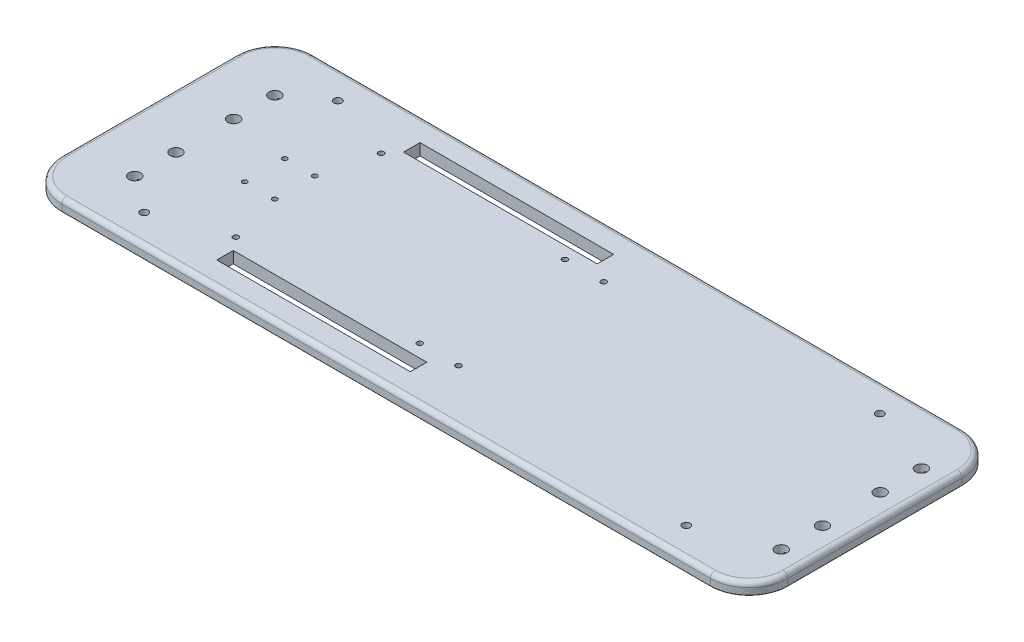
SolidWorks part; units mm, degrees
ref_plane "Alzado" through (0, 0, 0) normal (0, 0, 1) x (1, 0, 0)
ref_plane "Planta" through (0, 0, 0) normal (0, 1, 0) x (1, 0, 0)
ref_plane "Vista lateral" through (0, 0, 0) normal (1, 0, 0) x (0, 0, -1)
sketch "Croquis1" plane through (0, 0, 0) normal (0, 1, 0) x (1, 0, 0)
  line L1 (-187.5, -65) -> (187.5, -65)
  line L2 (-187.5, -65) -> (-187.5, 65)
  line L3 (-187.5, 65) -> (187.5, 65)
  line L4 (187.5, -65) -> (187.5, 65)
  line L5 (-187.5, -65) -> (187.5, 65) construction
  line L6 (-187.5, 65) -> (187.5, -65) construction
  point P0 (0, 0)
  dimension "D1" = 375
  dimension "D2" = 130
extrude "Saliente-Extruir1" add sketch "Croquis1" along normal blind 6
sketch "Croquis2" plane through (0, 6, 0) normal (0, 1, 0) x (1, 0, 0)
  line L0 (-158.7, -36.2) -> (-158.7, -14.9) construction
  line L1 (-187.5, -65) -> (-158.7, -65) construction
  line L2 (-187.5, -65) -> (-187.5, -36.2) construction
  line L3 (-187.5, -36.2) -> (-158.7, -36.2) construction
  line L4 (-158.7, -65) -> (-158.7, -36.2) construction
  line L5 (-55, 0) -> (55, 0) construction
  circle A0 centre (-158.7, -36.2) radius 3
  circle A1 centre (-158.7, -14.9) radius 1.5
  circle A2 centre (-158.7, 36.2) radius 3
  circle A3 centre (-158.7, 14.9) radius 1.5
  dimension "D3" = 6
  dimension "D5" = 3
  dimension "D1" = 28.8
  dimension "D2" = 28.8
  dimension "D4" = 21.3
extrude "Cortar-Extruir1" cut sketch "Croquis2" against normal blind 10
sketch "Croquis3" plane through (0, 6, 0) normal (0, 1, 0) x (1, 0, 0)
  line L0 (-158.7, -36.2) -> (187.5, -36.2) construction
  line L1 (187.5, -65) -> (187.5, 65) construction
  line L2 (175.3, -36.2) -> (175.3, -14.9) construction
  line L3 (175.3, -14.9) -> (-158.7, -14.9) construction
  line L4 (-55, 0) -> (55, 0) construction
  circle A0 centre (175.3, -36.2) radius 3
  circle A1 centre (175.3, -14.9) radius 1.5
  circle A2 centre (175.3, 14.9) radius 1.5
  circle A3 centre (175.3, 36.2) radius 3
  dimension "D1" = 6
  dimension "D2" = 12.2
  dimension "D4" = 3
  dimension "D3" = 21.3
extrude "Cortar-Extruir2" cut sketch "Croquis3" against normal blind 10
sketch "Croquis4" plane through (0, 0, 0) normal (0, -1, 0) x (1, 0, 0)
  line L0 (174.05, 41.7) -> (174.05, 30.7)
  line L1 (-159.95, 41.7) -> (-157.45, 41.7)
  line L2 (-159.95, 41.7) -> (-159.95, 30.7)
  line L3 (-159.95, 30.7) -> (-157.45, 30.7)
  line L4 (-157.45, 41.7) -> (-157.45, 30.7)
  line L5 (-159.95, 41.7) -> (-157.45, 30.7) construction
  line L6 (-159.95, 30.7) -> (-157.45, 41.7) construction
  line L7 (-158.7, 36.2) -> (175.3, 36.2) construction
  line L8 (-158.7, 36.2) -> (-158.7, -36.2) construction
  line L9 (-158.7, -36.2) -> (175.3, -36.2) construction
  line L10 (175.3, 36.2) -> (175.3, -36.2) construction
  line L11 (174.05, 41.7) -> (176.55, 41.7)
  line L12 (176.55, 41.7) -> (176.55, 30.7)
  line L13 (174.05, 30.7) -> (176.55, 30.7)
  line L14 (174.05, -30.7) -> (174.05, -41.7)
  line L15 (174.05, -30.7) -> (176.55, -30.7)
  line L16 (176.55, -30.7) -> (176.55, -41.7)
  line L17 (174.05, -41.7) -> (176.55, -41.7)
  line L18 (-159.95, -30.7) -> (-159.95, -41.7)
  line L19 (-159.95, -30.7) -> (-157.45, -30.7)
  line L20 (-157.45, -30.7) -> (-157.45, -41.7)
  line L21 (-159.95, -41.7) -> (-157.45, -41.7)
  point P0 (-158.7, 36.2)
  dimension "D1" = 2.5
  dimension "D2" = 11
  dimension "D3" = 2
  dimension "D4" = 2
extrude "Cortar-Extruir3" cut sketch "Croquis4" against normal blind 2.5
fillet "Redondeo1" radius 0.2 88 edges at (-159.95, 1.25, -38.9272) (-157.45, 1.25, -38.9272) (-157.45, 1.25, -33.4728) (-159.95, 1.25, -33.4728) (-157.45, 1.25, 33.4728) (-159.95, 1.25, 33.4728) (174.05, 1.25, -38.9272) (176.55, 1.25, -38.9272) (176.55, 1.25, -33.4728) (174.05, 1.25, -33.4728) (174.05, 1.25, 33.4728) (176.55, 1.25, 33.4728) (176.55, 1.25, 38.9272) (174.05, 1.25, 38.9272) (-159.95, 1.25, 38.9272) (-157.45, 1.25, 38.9272) (-158.7, 2.5, -39.2) (-157.45, 2.5, -40.3136) (-158.7, 2.5, -41.7) (-159.95, 2.5, -40.3136) (-158.7, 2.5, -33.2) (-159.95, 2.5, -32.0864) (-158.7, 2.5, -30.7) (-157.45, 2.5, -32.0864) (-157.45, 2.5, 32.0864) (-158.7, 2.5, 30.7) (-159.95, 2.5, 32.0864) (-158.7, 2.5, 33.2) (175.3, 2.5, -39.2) (176.55, 2.5, -40.3136) (175.3, 2.5, -41.7) (174.05, 2.5, -40.3136) (175.3, 2.5, -33.2) (174.05, 2.5, -32.0864) (175.3, 2.5, -30.7) (176.55, 2.5, -32.0864) (175.3, 2.5, 33.2) (176.55, 2.5, 32.0864) (175.3, 2.5, 30.7) (174.05, 2.5, 32.0864) (175.3, 2.5, 39.2) (174.05, 2.5, 40.3136) (175.3, 2.5, 41.7) (176.55, 2.5, 40.3136) (0, 0, -65) (-187.5, 0, 0) (0, 0, 65) (187.5, 0, 0) (-158.7, 0, 13.4) (-158.7, 0, -16.4) (175.3, 0, -16.4) (175.3, 0, 13.4) (-155.7, 0, 36.2) (-157.45, 0, 40.3136) (-158.7, 0, 41.7) (-159.95, 0, 40.3136) (-161.7, 0, 36.2) (-159.95, 0, 32.0864) (-158.7, 0, 30.7) (-157.45, 0, 32.0864) (175.3, 0, 30.7) (176.55, 0, 32.0864) (178.3, 0, 36.2) (176.55, 0, 40.3136) (175.3, 0, 41.7) (174.05, 0, 40.3136) (172.3, 0, 36.2) (174.05, 0, 32.0864) (175.3, 0, -41.7) (176.55, 0, -40.3136) (178.3, 0, -36.2) (176.55, 0, -32.0864) (175.3, 0, -30.7) (174.05, 0, -32.0864) (172.3, 0, -36.2) (174.05, 0, -40.3136) (-158.7, 0, -41.7) (-157.45, 0, -40.3136) (-155.7, 0, -36.2) (-157.45, 0, -32.0864) (-158.7, 0, -30.7) (-159.95, 0, -32.0864) (-161.7, 0, -36.2) (-159.95, 0, -40.3136) (-159.95, 2.5, 40.3136) (-158.7, 2.5, 41.7) (-157.45, 2.5, 40.3136) (-158.7, 2.5, 39.2)
fillet "Redondeo2" radius 20 8 edges at (-187.4414, 0.0586, 64.9414) (-187.4414, 0.0586, -64.9414) (187.4414, 0.0586, -64.9414) (187.4414, 0.0586, 64.9414) (187.5, 3.1, 65) (187.5, 3.1, -65) (-187.5, 3.1, -65) (-187.5, 3.1, 65)
fillet "Redondeo3" radius 2.5 8 edges at (-181.6421, 6, 59.1421) (-187.5, 6, 0) (-181.6421, 6, -59.1421) (0, 6, -65) (181.6421, 6, -59.1421) (187.5, 6, 0) (181.6421, 6, 59.1421) (0, 6, 65)
sketch "Croquis5" plane through (0, 6, 0) normal (0, 1, 0) x (1, 0, 0)
  line L0 (0, 0) -> (-140, 0) construction
  line L1 (-140, 0) -> (-140, 50) construction
  line L2 (-167.5, 65) -> (167.5, 65) construction
  line L3 (0, -55) -> (0, 55) construction
  circle A0 centre (-140, 50) radius 2
  circle A1 centre (-140, -50) radius 2
  circle A2 centre (140, -50) radius 2
  circle A3 centre (140, 50) radius 2
  dimension "D3" = 4
  dimension "D1" = 140
  dimension "D2" = 15
extrude "Cortar-Extruir4" cut sketch "Croquis5" against normal blind 10
sketch "Croquis6" plane through (0, 6, 0) normal (0, 1, 0) x (1, 0, 0)
  line L0 (-140, -50) -> (-140, -52.5) construction
  line L1 (-140, -52.5) -> (-100, -52.5) construction
  line L2 (-100, -52.5) -> (-100, -44)
  line L3 (-100, -44) -> (0, -44)
  line L4 (0, -44) -> (0, -52.5)
  line L5 (0, -52.5) -> (-100, -52.5)
  line L6 (-55, 0) -> (55, 0) construction
  line L7 (0, 44) -> (0, 52.5)
  line L8 (-100, 44) -> (0, 44)
  line L9 (-100, 52.5) -> (-100, 44)
  line L10 (0, 52.5) -> (-100, 52.5)
  dimension "D1" = 40
  dimension "D2" = 2.5
  dimension "D3" = 8.5
  dimension "D4" = 100
extrude "Cortar-Extruir5" cut sketch "Croquis6" against normal blind 10
sketch "Croquis7" plane through (0, 6, 0) normal (0, 1, 0) x (1, 0, 0)
  circle A0 centre (-127.8, 10.4) radius 1.25
  circle A1 centre (-112.3, 10.4) radius 1.25
  circle A2 centre (-112.3, -10.3) radius 1.25
  circle A3 centre (-127.8, -10.3) radius 1.25
  circle A4 centre (-105.3, 37.65) radius 1.4
  circle A5 centre (-10.3, 37.65) radius 1.4
  circle A6 centre (9.7, 37.65) radius 1.4
  circle A7 centre (9.7, -37.35) radius 1.4
  circle A8 centre (-10.3, -37.35) radius 1.4
  circle A9 centre (-105.3, -37.35) radius 1.4
extrude "Cortar-Extruir6" cut sketch "Croquis7" against normal blind 3
sketch "Croquis8" plane through (0, 6, 0) normal (0, 1, 0) x (1, 0, 0)
  circle A0 centre (-158.7, 14.9) radius 3
  circle A1 centre (-158.7, -14.9) radius 3
  circle A2 centre (175.3, 14.9) radius 3
  circle A3 centre (175.3, -14.9) radius 3
  dimension "D1" = 6
  dimension "D2" = 6
  dimension "D3" = 6
  dimension "D4" = 6
extrude "Cortar-Extruir7" cut sketch "Croquis8" against normal blind 8
